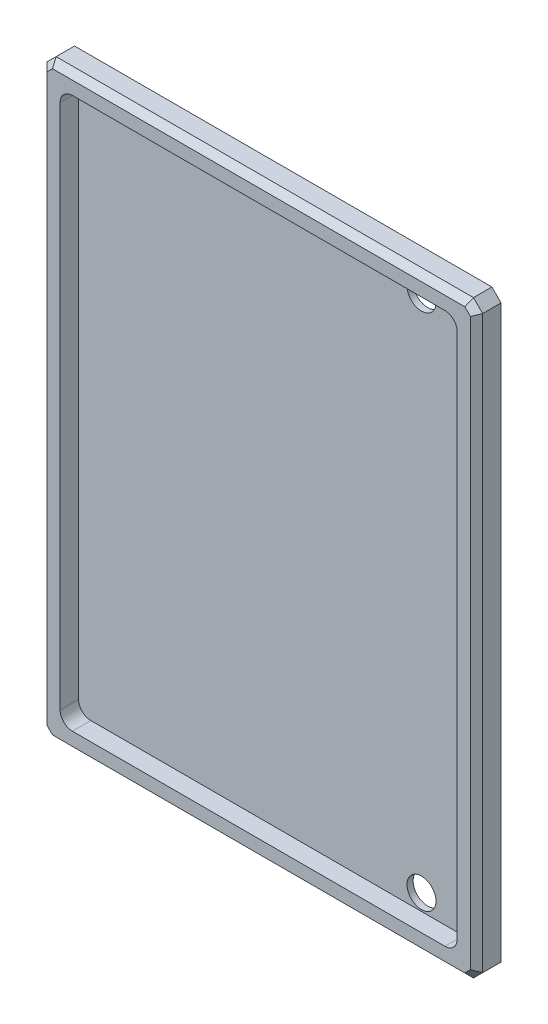
SolidWorks part; units mm, degrees
material "AISI 304"
ref_plane "Front Plane" through (0, 0, 0) normal (0, 0, 1) x (1, 0, 0)
ref_plane "Top Plane" through (0, 0, 0) normal (0, 1, 0) x (1, 0, 0)
ref_plane "Right Plane" through (0, 0, 0) normal (1, 0, 0) x (0, 0, -1)
sketch "Sketch1" plane through (0, 0, 0) normal (0, 0, 1) x (1, 0, 0)
  line L1 (112.7125, -152.4) -> (-112.7125, -152.4)
  line L2 (112.7125, -152.4) -> (112.7125, 152.4)
  line L3 (112.7125, 152.4) -> (-112.7125, 152.4)
  line L4 (-112.7125, -152.4) -> (-112.7125, 152.4)
  line L5 (112.7125, -152.4) -> (-112.7125, 152.4) construction
  line L6 (112.7125, 152.4) -> (-112.7125, -152.4) construction
  point P0 (0, 0)
  dimension "D1" = 304.8
  dimension "D2" = 225.425
extrude "Boss-Extrude1" add sketch "Sketch1" along normal blind 12.7
sketch "Sketch2" plane through (0, 0, 12.7) normal (0, 0, 1) x (1, 0, 0)
  line L0 (-112.7125, 152.4) -> (-112.7125, -152.4) construction
  line L1 (96.3625, -142.4) -> (-96.3625, -142.4)
  line L2 (102.7125, -136.05) -> (102.7125, 136.05)
  line L3 (96.3625, 142.4) -> (-96.3625, 142.4)
  line L4 (-102.7125, -136.05) -> (-102.7125, 136.05)
  line L5 (102.7125, -142.4) -> (-102.7125, 142.4) construction
  line L6 (102.7125, 142.4) -> (-102.7125, -142.4) construction
  line L7 (112.7125, 152.4) -> (-112.7125, 152.4) construction
  arc A0 (-96.3625, -142.4) -> (-102.7125, -136.05) centre (-96.3625, -136.05) cw
  arc A1 (96.3625, -142.4) -> (102.7125, -136.05) centre (96.3625, -136.05) ccw
  arc A2 (102.7125, 136.05) -> (96.3625, 142.4) centre (96.3625, 136.05) ccw
  arc A3 (-96.3625, 142.4) -> (-102.7125, 136.05) centre (-96.3625, 136.05) ccw
  point P0 (0, 0)
  dimension "D3" = 6.35
  dimension "D1" = 10
  dimension "D2" = 10
extrude "Cut-Extrude1" cut sketch "Sketch2" against normal blind 9.525
sketch "Sketch4" plane through (0, 0, 0) normal (0, 0, -1) x (-1, 0, 0)
  line L1 (-112.7125, -152.4) -> (-112.7125, 152.4) construction
  line L2 (0, 0) -> (-117.2439, 0) construction
  line L3 (96.3625, -142.4) -> (-96.3625, -142.4) construction
  circle A0 centre (-74.7125, -134.05) radius 7.5
  circle A1 centre (-74.7125, 134.05) radius 7.5
  dimension "D1" = 15
  dimension "D2" = 8.35
  dimension "D3" = 38
  dimension "D4" = 0
extrude "Cut-Extrude3" cut sketch "Sketch4" against normal through all
hole_wizard "M4x0.7 Tapped Hole1" positions "Sketch10" profile "Sketch11" tap size "M4x0.7" standard "ANSI Metric"
sketch "Sketch10" plane through (0, 0, 0) normal (0, 0, -1) x (-1, 0, 0)
  line L0 (112.7125, 152.4) -> (112.7125, -152.4) construction
  line L1 (-112.7125, 152.4) -> (112.7125, 152.4) construction
  point P0 (109.5375, -113.6)
  point P2 (109.5375, 113.6)
  dimension "D1" = 3.175
  dimension "D2" = 38.8
  dimension "D3" = 266
sketch "Sketch11" plane through (-109.5375, -113.6, 0) normal (1, 0, 0) x (0, 1, 0)
  line L0 (0, 0) -> (0, 6.3914)
  line L1 (0, 6.3914) -> (1.65, 5.4)
  line L2 (1.65, 5.4) -> (1.65, 0)
  line L5 (1.65, 0) -> (0, 0)
  line L10 (0, 6.3914) -> (-1.65, 5.4) construction
  line L11 (0, -6.35) -> (0, 107.95) construction
  dimension "Tap Drill Dia." = 3.3
  dimension "Tap Drill Depth" = 5.4
  dimension "Drill Angle" = 118
cosmetic thread "Hole Thread1" parameters "D1"=3, "D2"=4.3
cosmetic thread "Hole Thread2" parameters "D1"=3, "D2"=4.3
chamfer "Chamfer1" distance 4.7625 angle 45 4 edges at (-112.7125, 152.4, 6.35) (112.7125, 152.4, 6.35) (112.7125, -152.4, 6.35) (-112.7125, -152.4, 6.35)
chamfer "Chamfer2" distance 3.175 angle 45 8 edges at (110.3313, -150.0188, 12.7) (112.7125, 0, 12.7) (110.3313, 150.0187, 12.7) (0, 152.4, 12.7) (-110.3312, 150.0187, 12.7) (-112.7125, 0, 12.7) (-110.3313, -150.0188, 12.7) (0, -152.4, 12.7)
